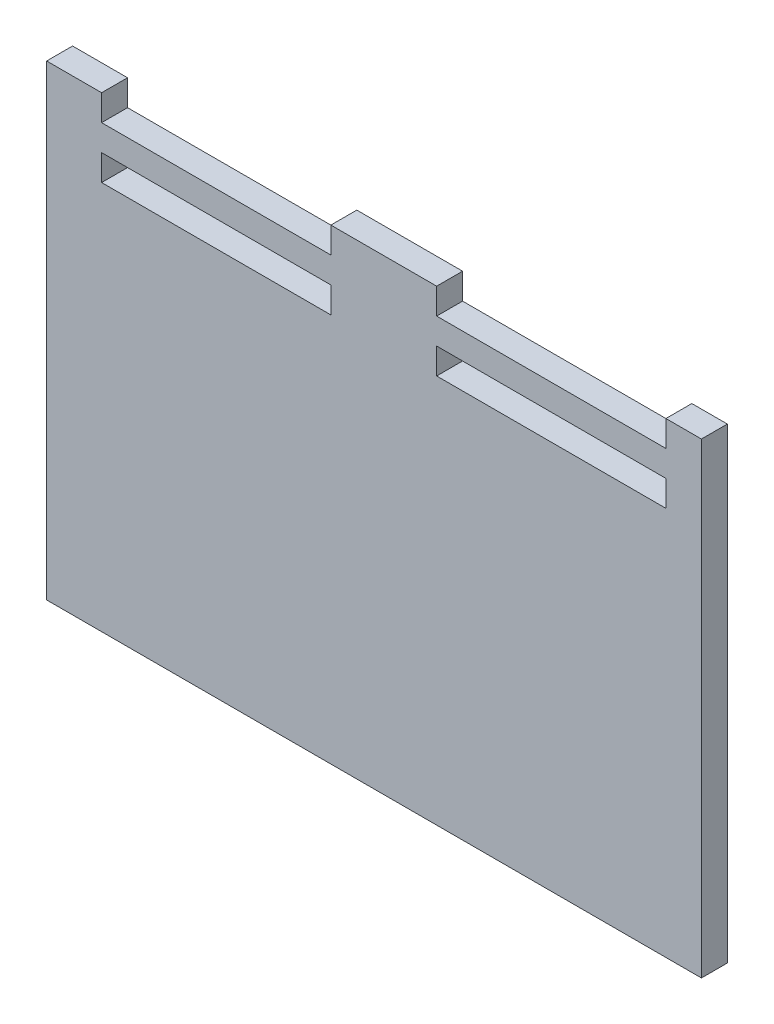
SolidWorks part; units mm, degrees
ref_plane "Front Plane" through (0, 0, 0) normal (0, 0, 1) x (1, 0, 0)
ref_plane "Top Plane" through (0, 0, 0) normal (0, 1, 0) x (1, 0, 0)
ref_plane "Right Plane" through (0, 0, 0) normal (1, 0, 0) x (0, 0, -1)
sketch "Sketch1" plane through (0, 0, 0) normal (0, 0, 1) x (1, 0, 0)
  line L1 (0, 0) -> (304.8, 0)
  line L2 (0, 0) -> (0, 228.6)
  line L3 (0, 228.6) -> (304.8, 228.6)
  line L4 (304.8, 0) -> (304.8, 228.6)
  dimension "D1" = 304.8
  dimension "D2" = 228.6
extrude "Boss-Extrude1" add sketch "Sketch1" along normal blind 12.7
sketch "Sketch6" plane through (0, 0, 12.7) normal (0, 0, 1) x (1, 0, 0)
  line L0 (0, 114.3) -> (304.8, 114.3) construction
  line L1 (0, 228.6) -> (0, 0) construction
  line L2 (304.8, 0) -> (304.8, 228.6) construction
sketch "Sketch7" plane through (0, 0, 12.7) normal (0, 0, 1) x (1, 0, 0)
  line L1 (14.224, 228.6) -> (126.492, 228.6)
  line L2 (14.224, 228.6) -> (14.224, 215.9)
  line L3 (14.224, 215.9) -> (126.492, 215.9)
  line L4 (0, 228.6) -> (0, 0)
  line L5 (0, 0) -> (304.8, 0)
  line L6 (304.8, 0) -> (304.8, 228.6)
  line L7 (304.8, 228.6) -> (0, 228.6)
  line L8 (0, 228.6) -> (0, 0)
  line L9 (0, 0) -> (304.8, 0)
  line L10 (304.8, 0) -> (304.8, 228.6)
  line L11 (304.8, 228.6) -> (0, 228.6)
  line L12 (126.492, 228.6) -> (126.492, 215.9)
  line L13 (178.308, 228.6) -> (290.576, 228.6)
  line L14 (178.308, 228.6) -> (178.308, 215.9)
  line L15 (178.308, 215.9) -> (290.576, 215.9)
  line L16 (290.576, 228.6) -> (290.576, 215.9)
  line L17 (14.224, 203.2) -> (126.492, 203.2)
  line L18 (14.224, 203.2) -> (14.224, 190.5)
  line L19 (14.224, 190.5) -> (126.492, 190.5)
  line L20 (126.492, 203.2) -> (126.492, 190.5)
  line L21 (178.308, 203.2) -> (290.576, 203.2)
  line L22 (178.308, 203.2) -> (178.308, 190.5)
  line L23 (178.308, 190.5) -> (290.576, 190.5)
  line L24 (290.576, 203.2) -> (290.576, 190.5)
  point P20 (70.358, 203.2)
  line M17 (304.8, 228.6) -> (0, 228.6)
  dimension "D2" = 14.224
  dimension "D3" = 112.268
  dimension "D4" = 112.268
  dimension "D5" = 14.224
  dimension "D6" = 12.7
  dimension "D7" = 12.7
  dimension "D8" = 12.7
  dimension "D9" = 112.268
  dimension "D10" = 112.268
  dimension "D11" = 12.7
  dimension "D12" = 12.7
  dimension "D1" = 0
extrude "Cut-Extrude2" cut sketch "Sketch7" against normal blind 12.7 contours L12 L2 L3 M17 | L15 L16 L13 L14 | L18 L17 L20 L19 | L22 L21 L24 L23 region at (70.358, 222.25, 12.7)
sketch "Sketch8" plane through (0, 0, 12.7) normal (0, 0, 1) x (1, 0, 0)
  line L1 (304.8, 228.6) -> (307.975, 228.6)
  line L2 (304.8, 228.6) -> (304.8, 0)
  line L3 (304.8, 0) -> (307.975, 0)
  line L4 (307.975, 228.6) -> (307.975, 0)
  line L5 (0, 228.6) -> (-12.7, 228.6)
  line L6 (0, 228.6) -> (0, 0)
  line L7 (0, 0) -> (-12.7, 0)
  line L8 (-12.7, 228.6) -> (-12.7, 0)
  line L12 (290.576, 215.9) -> (178.308, 215.9)
  line L13 (178.308, 215.9) -> (178.308, 228.6)
  line L14 (178.308, 228.6) -> (126.492, 228.6)
  line L15 (126.492, 228.6) -> (126.492, 215.9)
  line L16 (126.492, 215.9) -> (14.224, 215.9)
  line L17 (14.224, 215.9) -> (14.224, 228.6)
  line L18 (14.224, 228.6) -> (0, 228.6)
  line L19 (0, 228.6) -> (0, 0)
  line L20 (0, 0) -> (304.8, 0)
  line L21 (304.8, 0) -> (304.8, 228.6)
  line L22 (304.8, 228.6) -> (290.576, 228.6)
  line L23 (290.576, 228.6) -> (290.576, 215.9)
  line L24 (290.576, 215.9) -> (178.308, 215.9)
  line L25 (178.308, 215.9) -> (178.308, 228.6)
  line L26 (178.308, 228.6) -> (126.492, 228.6)
  line L27 (126.492, 228.6) -> (126.492, 215.9)
  line L28 (126.492, 215.9) -> (14.224, 215.9)
  line L29 (14.224, 215.9) -> (14.224, 228.6)
  line L30 (14.224, 228.6) -> (0, 228.6)
  line L31 (0, 228.6) -> (0, 0)
  line L32 (0, 0) -> (304.8, 0)
  line L33 (304.8, 0) -> (304.8, 228.6)
  line L34 (304.8, 228.6) -> (290.576, 228.6)
  line L35 (290.576, 228.6) -> (290.576, 215.9)
  line M22 (0, 228.6) -> (0, 0)
  line M24 (304.8, 0) -> (304.8, 228.6)
  dimension "D2" = 12.7
  dimension "D3" = 3.175
  dimension "D1" = 0
extrude "Boss-Extrude2" add sketch "Sketch8" against normal blind 12.7 contours L5 L8 L7 M22 | L4 L1 L3 M24 region at (306.3875, 114.3, 12.7) region at (-6.35, 114.3, 12.7)
